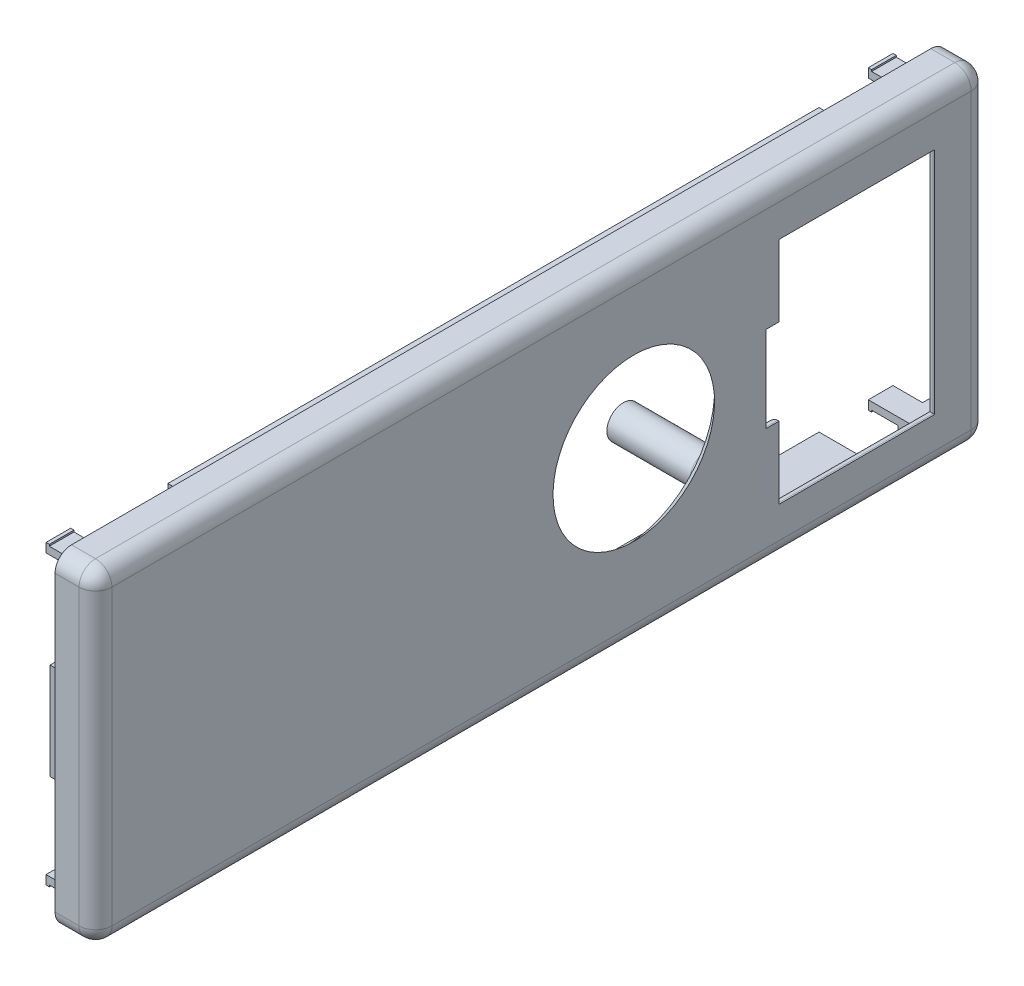
SolidWorks part; units mm, degrees
ref_plane "Front Plane" through (0, 0, 0) normal (0, 0, 1) x (1, 0, 0)
ref_plane "Top Plane" through (0, 0, 0) normal (0, 1, 0) x (1, 0, 0)
ref_plane "Right Plane" through (0, 0, 0) normal (1, 0, 0) x (0, 0, -1)
sketch "Sketch1" plane through (14.6764, 0, 0) normal (1, 0, 0) x (0, 0, -1)
  line L0 (128.8339, 33.2359) -> (-3.8585, 33.2359)
  line L1 (131.3739, 30.6959) -> (131.3739, -14.605)
  line L2 (128.8339, -17.145) -> (-3.8585, -17.145)
  line L3 (-6.3985, -14.605) -> (-6.3985, 30.6959)
  line L4 (99.1697, 25.6826) -> (123.1857, 25.6826)
  line L5 (123.1857, 25.6826) -> (123.1857, -9.7334)
  line L6 (123.1857, -9.7334) -> (99.1697, -9.7334)
  line L7 (99.1697, -9.7334) -> (99.1697, 25.6826)
  line L8 (122.6777, -9.2254) -> (99.6777, -9.2254) construction
  line L9 (122.6777, 25.1746) -> (122.6777, -9.2254) construction
  line L10 (99.6777, -9.2254) -> (99.6777, 25.1746) construction
  line L11 (99.6777, 25.1746) -> (122.6777, 25.1746) construction
  arc A0 (-3.8585, 33.2359) -> (-6.3985, 30.6959) centre (-3.8585, 30.6959) ccw
  arc A1 (-6.3985, -14.605) -> (-3.8585, -17.145) centre (-3.8585, -14.605) ccw
  arc A2 (128.8339, -17.145) -> (131.3739, -14.605) centre (128.8339, -14.605) ccw
  arc A3 (128.8339, 33.2359) -> (131.3739, 30.6959) centre (128.8339, 30.6959) cw
  circle A4 centre (76.727, 8.9746) radius 11.43
  dimension "D1" = 22.86
  dimension "D2" = 0.508
  dimension "D3" = 0.508
  dimension "D4" = 0.508
  dimension "D5" = 0.508
extrude "Boss-Extrude1" add sketch "Sketch1" along normal up to surface (1.4964 mm away)
sketch "Sketch2" plane through (16.1728, 0, 0) normal (1, 0, 0) x (0, 0, -1)
  line L0 (99.1697, 14.6596) -> (97.1377, 14.6596)
  line L1 (99.1697, 25.6826) -> (99.1697, -9.7334) construction
  line L2 (97.1377, 14.6596) -> (97.1377, 1.3896)
  line L3 (97.1377, 1.3896) -> (99.1697, 1.3896)
  line L4 (99.1697, 1.3896) -> (99.1697, 14.6596)
  line L5 (98.0562, 14.0246) -> (102.0562, 14.0246) construction
  line L6 (102.0562, 2.0246) -> (98.0562, 2.0246) construction
  dimension "D1" = 0.635
  dimension "D2" = 0.635
  dimension "D3" = 2.032
extrude "Cut-Extrude1" cut sketch "Sketch2" against normal up to next
sketch "Sketch3" plane through (14.6764, 0, 0) normal (-1, 0, 0) x (0, 0, 1)
  circle A0 centre (-125.0239, 23.2146) radius 1.27
  circle A1 centre (-97.0839, 23.2146) radius 1.27
  circle A2 centre (-97.0839, -7.2654) radius 1.27
  circle A3 centre (-125.0239, -7.2654) radius 1.27
  dimension "D1" = 2.54
extrude "Cut-Extrude2" cut sketch "Sketch3" against normal blind 1.27
chamfer "Chamfer1" distance 2.54 angle 45 1 edges at (14.6764, 20.4046, -76.727)
sketch "Sketch4" plane through (14.6764, 0, 0) normal (-1, 0, 0) x (0, 0, 1)
  circle A0 centre (-90.727, 18.2246) radius 2.54
  circle A1 centre (-64.227, 18.2246) radius 2.54
  circle A2 centre (-64.227, -2.2754) radius 2.54
  circle A3 centre (-90.727, -2.2754) radius 2.54
  circle A4 centre (-90.727, 18.2246) radius 1.4732
  circle A5 centre (-64.227, 18.2246) radius 1.4732
  circle A6 centre (-90.727, -2.2754) radius 1.4732
  circle A7 centre (-64.227, -2.2754) radius 1.4732
  dimension "D1" = 5.08
  dimension "D2" = 2.9464
extrude "Boss-Extrude2" add sketch "Sketch4" along normal offset from surface (14.1219 mm away) 0.508
fillet "Fillet1" radius 1.27 4 edges at (14.6764, -4.8154, -90.727) (14.6764, -4.8154, -64.227) (14.6764, 19.7355, -62.1853) (14.6764, 15.6846, -90.727)
sketch "Sketch5" plane through (14.6764, 0, 0) normal (-1, 0, 0) x (0, 0, 1)
  line L0 (-128.8339, 33.2359) -> (3.8585, 33.2359)
  line L1 (6.3985, 30.6959) -> (6.3985, -14.605)
  line L2 (3.8585, -17.145) -> (-128.8339, -17.145)
  line L3 (-131.3739, -14.605) -> (-131.3739, 30.6959)
  line L4 (-128.8339, -15.24) -> (4.4935, -15.24)
  line L5 (4.4935, -15.24) -> (4.4935, 31.3309)
  line L6 (4.4935, 31.3309) -> (-128.8339, 31.3309)
  line L7 (-128.8339, 31.3309) -> (-128.8339, -15.24)
  arc A0 (-128.8339, 33.2359) -> (-131.3739, 30.6959) centre (-128.8339, 30.6959) ccw
  arc A1 (-128.8339, -17.145) -> (-131.3739, -14.605) centre (-128.8339, -14.605) cw
  arc A2 (3.8585, -17.145) -> (6.3985, -14.605) centre (3.8585, -14.605) ccw
  arc A3 (6.3985, 30.6959) -> (3.8585, 33.2359) centre (3.8585, 30.6959) ccw
extrude "Boss-Extrude3" add sketch "Sketch5" along normal up to surface (4.745 mm away)
sketch "Sketch6" plane through (9.9314, 0, 0) normal (-1, 0, 0) x (0, 0, 1)
  line L0 (-114.8727, -15.24) -> (-114.8727, -12.7)
  line L1 (4.4935, -15.24) -> (-128.8339, -15.24) construction
  line L2 (-114.8727, -12.7) -> (-14.3206, -12.7)
  line L3 (-14.3206, -12.7) -> (-14.3206, -15.24)
  line L4 (-114.8727, -15.24) -> (-14.3206, -15.24)
  line L5 (-114.8727, 31.3309) -> (-114.8727, 28.7909)
  line L6 (-128.8339, 31.3309) -> (4.4935, 31.3309) construction
  line L7 (-114.8727, 28.7909) -> (-14.3206, 28.7909)
  line L8 (-14.3206, 28.7909) -> (-14.3206, 31.3309)
  line L9 (-14.3206, 31.3309) -> (-114.8727, 31.3309)
  line L10 (4.4935, 8.0454) -> (4.4935, 15.5069)
  line L11 (4.4935, 31.3309) -> (4.4935, -15.24) construction
  line L12 (4.4935, 15.5069) -> (1.9535, 15.5069)
  line L13 (1.9535, 15.5069) -> (1.9535, 0.584)
  line L14 (1.9535, 0.584) -> (4.4935, 0.584)
  line L15 (4.4935, 0.584) -> (4.4935, 8.0454)
  dimension "D1" = 2.54
  dimension "D2" = 2.54
  dimension "D3" = 2.54
extrude "Boss-Extrude4" add sketch "Sketch6" against normal up to surface (4.745 mm away) up to face at (14.6764, 8.0454, -62.1702)
sketch "Sketch7" plane through (9.9314, 0, 0) normal (-1, 0, 0) x (0, 0, 1)
  line L0 (-114.8727, 28.7909) -> (-14.3206, 28.7909)
  line L1 (-14.3206, 28.7909) -> (-14.3206, 30.6959)
  line L2 (-14.3206, 28.7909) -> (-14.3206, 31.3309) construction
  line L3 (-14.3206, 30.6959) -> (-114.8727, 30.6959)
  line L4 (-114.8727, 31.3309) -> (-114.8727, 28.7909) construction
  line L5 (-114.8727, 30.6959) -> (-114.8727, 28.7909)
  line L6 (1.9535, 15.5069) -> (3.8585, 15.5069)
  line L7 (4.4935, 15.5069) -> (1.9535, 15.5069) construction
  line L8 (3.8585, 15.5069) -> (3.8585, 0.584)
  line L9 (1.9535, 0.584) -> (4.4935, 0.584) construction
  line L10 (3.8585, 0.584) -> (1.9535, 0.584)
  line L11 (1.9535, 0.584) -> (1.9535, 15.5069)
  line L12 (-14.3206, -12.7) -> (-14.3206, -14.605)
  line L13 (-14.3206, -15.24) -> (-14.3206, -12.7) construction
  line L14 (-14.3206, -14.605) -> (-114.8727, -14.605)
  line L15 (-114.8727, -12.7) -> (-114.8727, -15.24) construction
  line L16 (-114.8727, -14.605) -> (-114.8727, -12.7)
  line L17 (-114.8727, -12.7) -> (-14.3206, -12.7)
  dimension "D1" = 1.905
  dimension "D2" = 1.905
  dimension "D3" = 1.905
extrude "Boss-Extrude5" add sketch "Sketch7" along normal blind 3.302
sketch "Sketch8" plane through (9.9314, 0, 0) normal (-1, 0, 0) x (0, 0, 1)
  line L7 (-123.7539, 31.3309) -> (-123.7539, 29.5529)
  line L8 (-128.8339, 31.3309) -> (-114.8727, 31.3309) construction
  line L9 (-123.7539, 31.3309) -> (-123.7539, 30.5689) construction
  line L10 (-123.7539, 29.5529) -> (-128.8339, 29.5529)
  line L11 (-128.8339, -15.24) -> (-128.8339, 31.3309) construction
  line L12 (-128.8339, 29.5529) -> (-128.8339, 31.3309)
  line L13 (-128.8339, 31.3309) -> (-123.7539, 31.3309)
  line L14 (-123.7539, -15.24) -> (-123.7539, -13.462)
  line L15 (-114.8727, -15.24) -> (-128.8339, -15.24) construction
  line L16 (-123.7539, -14.478) -> (-123.7539, -15.24) construction
  line L17 (-123.7539, -13.462) -> (-128.8339, -13.462)
  line L18 (-128.8339, -13.462) -> (-128.8339, -15.24)
  line L19 (-128.8339, -15.24) -> (-123.7539, -15.24)
  line L20 (4.4935, -15.24) -> (4.4935, -13.462)
  line L21 (4.4935, 0.584) -> (4.4935, -15.24) construction
  line L22 (4.4935, -13.462) -> (-0.5865, -13.462)
  line L23 (-0.5865, -13.462) -> (-0.5865, -15.24)
  line L24 (-0.5865, -15.24) -> (-0.5865, -14.478) construction
  line L25 (4.4935, -15.24) -> (-14.3206, -15.24) construction
  line L26 (-0.5865, -15.24) -> (4.4935, -15.24)
  line L27 (4.4935, 31.3309) -> (-0.5865, 31.3309)
  line L28 (-14.3206, 31.3309) -> (4.4935, 31.3309) construction
  line L29 (-0.5865, 30.5689) -> (-0.5865, 31.3309) construction
  line L35 (-0.5865, 31.3309) -> (-0.5865, 29.5529)
  line L36 (-0.5865, 29.5529) -> (4.4935, 29.5529)
  line L37 (4.4935, 31.3309) -> (4.4935, 15.5069) construction
  line L38 (4.4935, 29.5529) -> (4.4935, 31.3309)
  dimension "D1" = 1.778
extrude "Boss-Extrude6" add sketch "Sketch8" against normal up to surface (4.745 mm away) up to face at (14.6764, 8.0454, -47.035)
sketch "Sketch9" plane through (9.9314, 0, 0) normal (-1, 0, 0) x (0, 0, 1)
  line L0 (-127.5639, -13.462) -> (-123.7539, -13.462)
  line L1 (-123.7539, -13.462) -> (-123.7539, -14.605)
  line L2 (-123.7539, -15.24) -> (-123.7539, -13.462) construction
  line L3 (-123.7539, -14.605) -> (-127.5639, -14.605)
  line L5 (-127.5639, -14.605) -> (-127.5639, -13.462)
  line L7 (-123.7539, -14.478) -> (-128.8339, -14.478) construction
  line L8 (-0.5865, -13.462) -> (-0.5865, -14.605)
  line L9 (-0.5865, -13.462) -> (-0.5865, -15.24) construction
  line L10 (-0.5865, -14.605) -> (3.2235, -14.605)
  line L12 (3.2235, -14.605) -> (3.2235, -13.462)
  line L13 (3.2235, -13.462) -> (-0.5865, -13.462)
  line L14 (3.2235, 29.5529) -> (3.2235, 30.6959)
  line L16 (3.2235, 30.6959) -> (-0.5865, 30.6959)
  line L17 (-0.5865, 31.3309) -> (-0.5865, 29.5529) construction
  line L18 (-0.5865, 30.6959) -> (-0.5865, 29.5529)
  line L19 (-0.5865, 29.5529) -> (3.2235, 29.5529)
  line L20 (-123.7539, 29.5529) -> (-123.7539, 30.6959)
  line L21 (-123.7539, 29.5529) -> (-123.7539, 31.3309) construction
  line L22 (-123.7539, 30.6959) -> (-127.5639, 30.6959)
  line L24 (-127.5639, 30.6959) -> (-127.5639, 29.5529)
  line L25 (-127.5639, 29.5529) -> (-123.7539, 29.5529)
  dimension "D1" = 0.127
  dimension "D2" = 3.81
extrude "Boss-Extrude7" add sketch "Sketch9" along normal blind 4.572
sketch "Sketch10" plane through (0, -14.605, 0) normal (0, -1, 0) x (1, 0, 0)
  line L0 (5.8674, -123.7539) -> (5.8674, -127.5639)
  line L1 (5.3594, -123.7539) -> (9.9314, -123.7539) construction
  line L2 (5.3594, -127.5639) -> (9.9314, -127.5639) construction
  line L3 (5.8674, -127.5639) -> (5.3594, -127.5639)
  line L4 (5.3594, -127.5639) -> (5.3594, -123.7539)
  line L5 (5.3594, -123.7539) -> (5.8674, -123.7539)
  line L6 (6.1214, -123.7539) -> (6.1214, -128.8339) construction
  line L7 (5.3594, -0.5865) -> (5.8674, -0.5865)
  line L8 (5.3594, -0.5865) -> (9.9314, -0.5865) construction
  line L9 (5.8674, -0.5865) -> (5.8674, 3.2235)
  line L10 (5.3594, 3.2235) -> (9.9314, 3.2235) construction
  line L11 (5.8674, 3.2235) -> (5.3594, 3.2235)
  line L12 (5.3594, 3.2235) -> (5.3594, -0.5865)
  line L13 (6.1214, -0.5865) -> (6.1214, 4.4935) construction
  dimension "D1" = 0.254
  dimension "D2" = 0.254
extrude "Boss-Extrude8" add sketch "Sketch10" along normal blind 0.254
sketch "Sketch11" plane through (0, 30.6959, 0) normal (0, 1, 0) x (1, 0, 0)
  line L0 (5.8681, 0.5865) -> (5.8674, -3.2235)
  line L1 (5.3594, 0.5865) -> (9.9314, 0.5865) construction
  line L2 (5.8674, -3.2235) -> (5.3594, -3.2235)
  line L3 (5.3594, -3.2235) -> (5.3594, 0.5865)
  line L4 (5.3594, 0.5865) -> (5.8681, 0.5865)
  line L5 (6.1214, 0.5865) -> (6.1214, -4.4935) construction
  line L6 (5.3594, 123.7539) -> (5.8674, 123.7539)
  line L7 (5.8674, 123.7539) -> (5.8674, 127.5639)
  line L8 (5.8674, 127.5639) -> (5.3594, 127.5639)
  line L9 (5.3594, 127.5639) -> (5.3594, 123.7539)
  line L10 (6.1214, 123.7539) -> (6.1214, 128.8339) construction
  dimension "D1" = 0.01
  dimension "D2" = 0.254
extrude "Boss-Extrude9" add sketch "Sketch11" along normal blind 0.254
fillet "Fillet2" radius 2.54 8 edges at (16.1728, -16.4011, -130.63) (16.1728, -17.145, -62.4877) (16.1728, -16.4011, 5.6545) (16.1728, 8.0454, 6.3985) (16.1728, 32.492, 5.6545) (16.1728, 33.2359, -62.4877) (16.1728, 32.492, -130.63) (16.1728, 8.0454, -131.3739)
sketch "Sketch12" plane through (0.5545, 0, 0) normal (-1, 0, 0) x (0, 0, 1)
  line L0 (-66.7275, 18.6709) -> (-63.7807, 15.7241)
  circle A0 centre (-64.227, 18.2246) radius 2.54 construction
  arc A1 (-63.7807, 15.7241) -> (-66.7275, 18.6709) centre (-64.227, 18.2246) cw
extrude "Cut-Extrude3" cut sketch "Sketch12" against normal blind 12.7
fillet "Fillet3" radius 1.27 8 edges at (14.6764, 25.6826, -111.1777) (14.6764, 14.6596, -98.1537) (14.6764, 20.1711, -99.1697) (14.6764, 8.0246, -97.1377) (14.6764, 1.3896, -98.1537) (14.6764, -4.1719, -99.1697) (14.6764, -9.7334, -111.1777) (14.6764, 7.9746, -123.1857)
